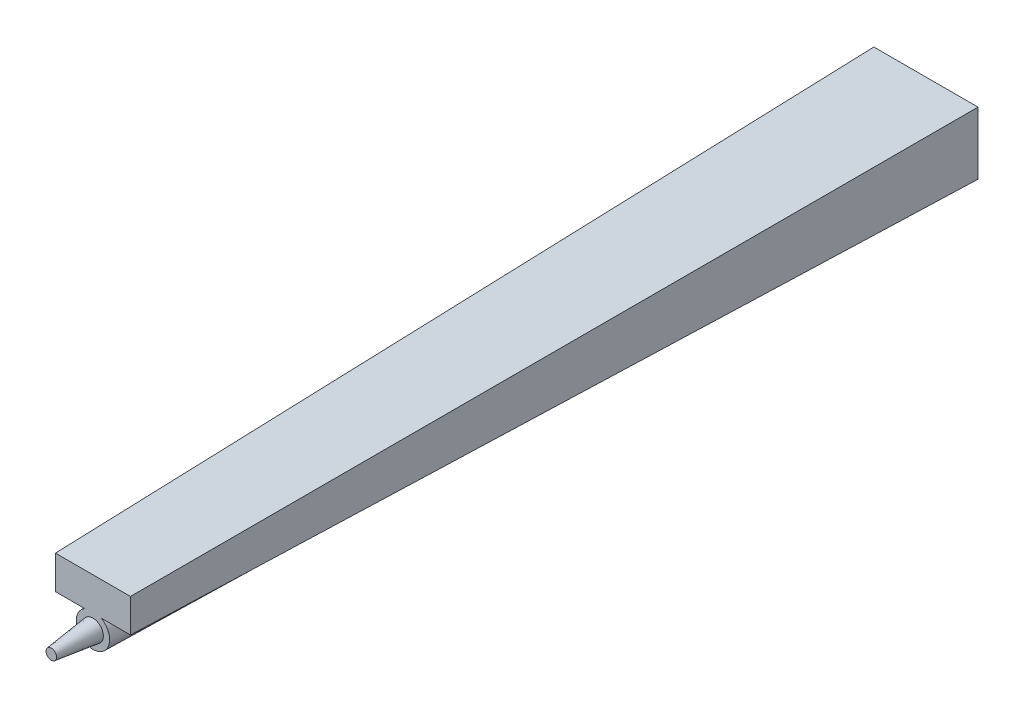
SolidWorks part; units mm, degrees
ref_plane "Front Plane" through (0, 0, 0) normal (0, 0, 1) x (1, 0, 0)
ref_plane "Top Plane" through (0, 0, 0) normal (0, 1, 0) x (1, 0, 0)
ref_plane "Right Plane" through (0, 0, 0) normal (1, 0, 0) x (0, 0, -1)
sketch "Sketch1" plane through (0, 0, 0) normal (0, 0, 1) x (1, 0, 0)
  line L1 (-6.35, -3.81) -> (6.35, -3.81)
  line L2 (-6.35, -3.81) -> (-6.35, 3.81)
  line L3 (-6.35, 3.81) -> (6.35, 3.81)
  line L4 (6.35, -3.81) -> (6.35, 3.81)
  line L5 (-6.35, -3.81) -> (6.35, 3.81) construction
  line L6 (-6.35, 3.81) -> (6.35, -3.81) construction
  circle A0 centre (0, -3.81) radius 3.81
  point P0 (0, 0)
  dimension "D1" = 12.7
  dimension "D2" = 7.62
extrude "Boss-Extrude1" add sketch "Sketch1" along normal blind 101.6 draft 1 contours L1 A0 | A0 L1 L4 L3 L2 | L1 A0 region at (0, 0.676, 0) region at (0, -5.427, 0) region at (0, -2.193, 0)
sketch "Sketch2" plane through (0, 0, 101.6) normal (0, 0, 1) x (1, 0, 0)
  circle A0 centre (0, -3.81) radius 1.27
  dimension "D1" = 2.54
extrude "Boss-Extrude2" add sketch "Sketch2" along normal blind 5.08 draft 7
